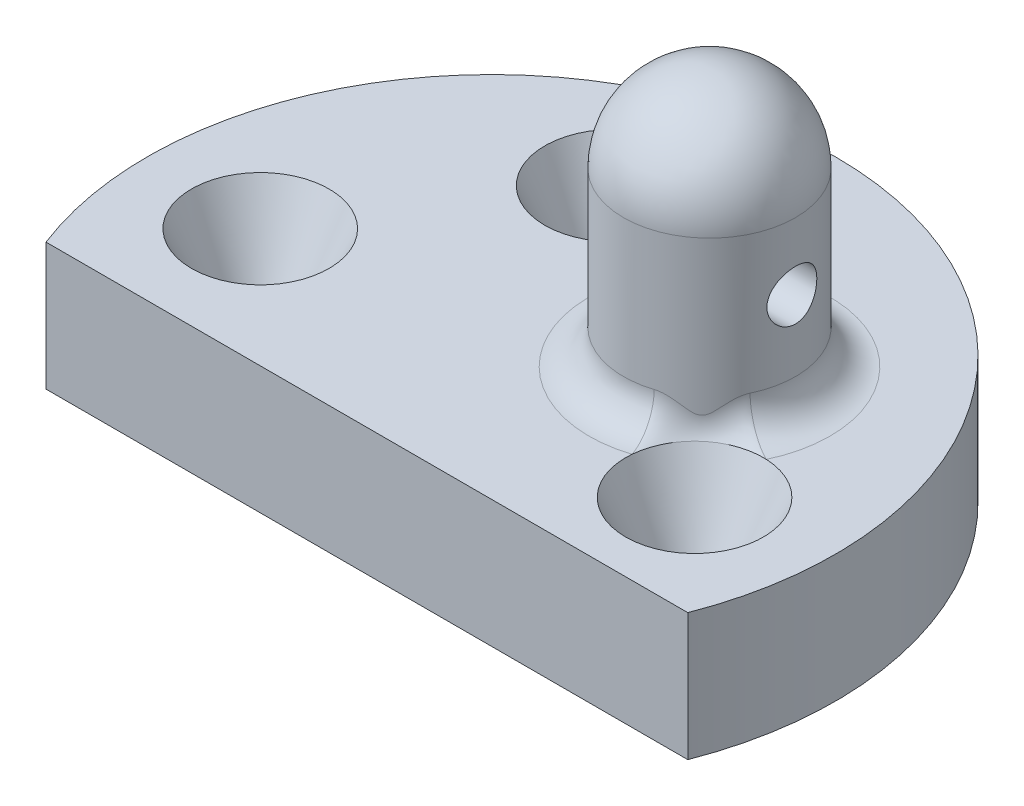
SolidWorks part; units mm, degrees
ref_plane "Plan de face" through (0, 0, 0) normal (0, 0, 1) x (1, 0, 0)
ref_plane "Plan de dessus" through (0, 0, 0) normal (0, 1, 0) x (1, 0, 0)
ref_plane "Plan de droite" through (0, 0, 0) normal (1, 0, 0) x (0, 0, -1)
sketch "Esquisse1" plane through (0, 0, 0) normal (0, 1, 0) x (1, 0, 0)
  line L0 (-18.6474, -7.23) -> (18.6474, -7.23)
  arc A0 (18.6474, -7.23) -> (-18.6474, -7.23) centre (0, 0) ccw
  dimension "D1" = 40
  dimension "D2" = 7.23
extrude "Boss.-Extru.1" add sketch "Esquisse1" along normal blind 7.4
sketch "Esquisse2" plane through (0, 7.4, 0) normal (0, 1, 0) x (1, 0, 0)
  circle A0 centre (6.9, 5.78) radius 5
  dimension "D1" = 10
  dimension "D2" = 6.9
  dimension "D3" = 5.78
extrude "Boss.-Extru.2" add sketch "Esquisse2" along normal blind 15
sketch "Esquisse3" plane through (0, 7.4, 0) normal (0, 1, 0) x (1, 0, 0)
  line L0 (-18.6474, -7.23) -> (18.6474, -7.23) construction
  circle A0 centre (-13.0958, -0.33) radius 1.95
  arc A1 (18.6474, -7.23) -> (-18.6474, -7.23) centre (0, 0) ccw construction
  circle A2 centre (13.0421, -1.23) radius 1.95
  circle A3 centre (-5, 12.1083) radius 1.95
  dimension "D1" = 3.9
  dimension "D4" = 3.9
  dimension "D7" = 3.9
  dimension "D2" = 13.1
  dimension "D3" = 6.9
  dimension "D5" = 13.1
  dimension "D6" = 6
  dimension "D8" = 13.1
  dimension "D9" = 5
extrude "Enlèv. mat.-Extru.1" cut sketch "Esquisse3" against normal through all
sketch "Esquisse4" plane through (0, 7.4, 0) normal (0, 1, 0) x (1, 0, 0)
  circle A0 centre (-5, 12.1083) radius 4
  circle A1 centre (-13.0958, -0.33) radius 4
  circle A2 centre (13.0421, -1.23) radius 4
  dimension "D1" = 8
  dimension "D2" = 8
  dimension "D3" = 8
extrude "Enlèv. mat.-Extru.2" cut sketch "Esquisse4" against normal blind 4.4 draft 25
sketch "Esquisse5" plane through (0, 0, 0) normal (1, 0, 0) x (0, 0, -1)
  line L0 (20, 7.4) -> (-7.23, 7.4) construction
  circle A0 centre (5.78, 13.5) radius 1.45
  dimension "D1" = 2.9
  dimension "D2" = 6.1
extrude "Enlèv. mat.-Extru.4" cut sketch "Esquisse5" along normal through all
fillet "Congé1" radius 5 1 edges at (6.9, 22.4, -0.78)
fillet "Congé2" radius 2 1 edges at (6.9, 7.4, -0.78)
